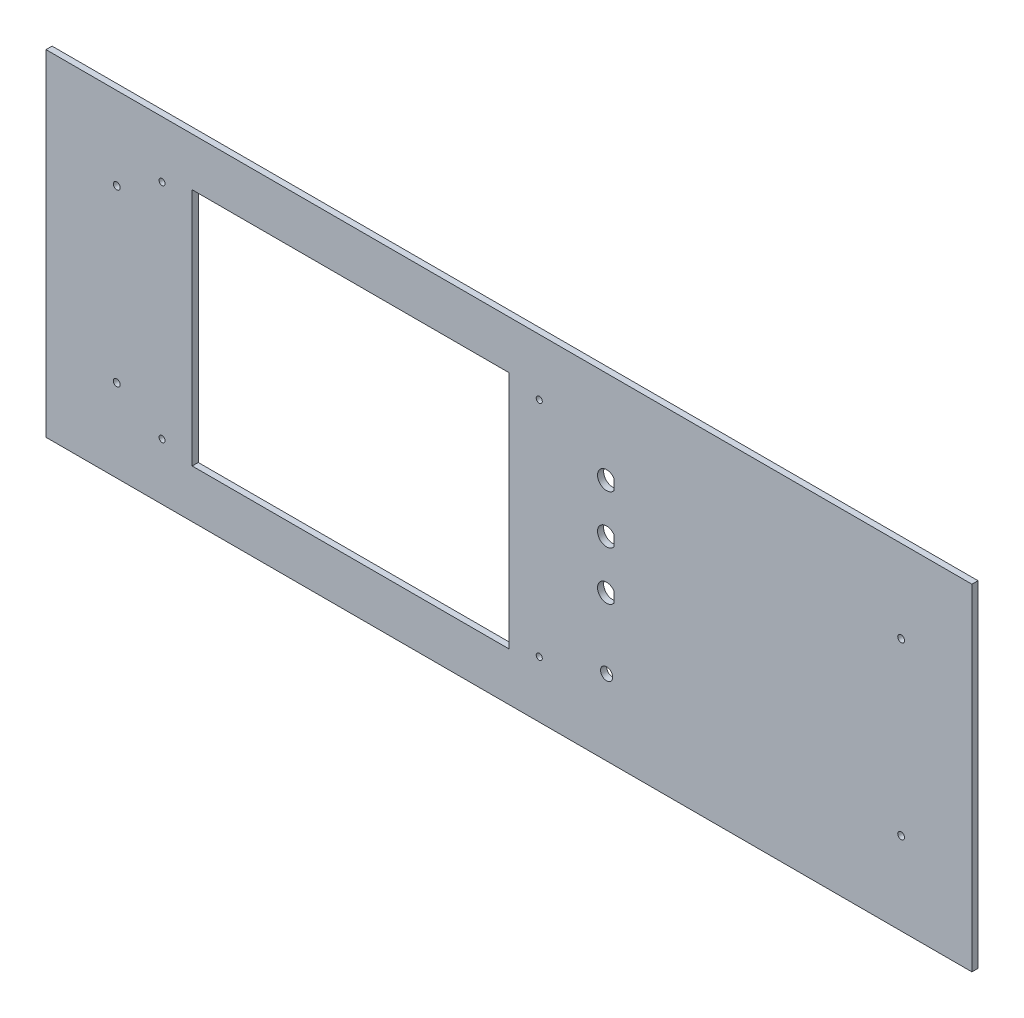
SolidWorks part; units mm, degrees
ref_plane "Front" through (0, 0, 0) normal (0, 0, 1) x (1, 0, 0)
ref_plane "Top" through (0, 0, 0) normal (0, 1, 0) x (1, 0, 0)
ref_plane "Right" through (0, 0, 0) normal (1, 0, 0) x (0, 0, -1)
sketch "Sketch1" plane through (0, 0, 0) normal (0, 0, 1) x (1, 0, 0)
  line L1 (0, 0) -> (482.6, 0)
  line L2 (0, 0) -> (0, 175.006)
  line L3 (0, 175.006) -> (482.6, 175.006)
  line L4 (482.6, 0) -> (482.6, 175.006)
  dimension "D1" = 175.006
  dimension "D2" = 482.6
sheet metal parameters "Sheet-Metal1" thickness 3.175 parameters "D1"=0.7366
base flange "Base-Flange" sketch "Sketch1" thickness 3.175 parameters "D1"=0.7366
ref_plane "Plane1" through (242.0937, 0, 0) normal (1, 0, 0) x (0, 0, -1)
sketch "Sketch2" plane through (0, 0, 3.175) normal (0, 0, 1) x (1, 0, 0)
  line L0 (482.6, 175.006) -> (0, 175.006) construction
  line L1 (76.2, 149.8473) -> (241.4016, 149.8473)
  line L2 (76.2, 149.8473) -> (76.2, 25.1587)
  line L3 (76.2, 25.1587) -> (241.4016, 25.1587)
  line L4 (241.4016, 149.8473) -> (241.4016, 25.1587)
  line L5 (0, 175.006) -> (0, 0) construction
  dimension "D1" = 165.2016
  dimension "D2" = 124.6886
  dimension "D3" = 25.1587
  dimension "D4" = 76.2
extrude "Cut-Extrude1" cut sketch "Sketch2" against normal through all normal cut yes
hole_wizard "1/8 (0.125) Diameter Hole1" positions "3DSketch1" profile "Sketch3" hole size "1/8" standard "Ansi Inch" end condition through all
sketch3d "3DSketch1"
  line L0 (76.2, 25.1587, 3.175) -> (241.4016, 25.1587, 3.175) construction
  line L1 (76.2, 149.8473, 3.175) -> (76.2, 25.1587, 3.175) construction
  point P0 (60.5028, 29.5021, 3.175)
  dimension "D1" = 4.3434
  dimension "D2" = 15.6972
sketch "Sketch3" plane through (60.5028, 29.5021, 3.175) normal (1, 0, 0) x (0, -1, 0)
  line L0 (0, 0) -> (0, 3.175)
  line L1 (0, 3.175) -> (1.5875, 3.175)
  line L2 (1.5875, 3.175) -> (1.5875, 0)
  line L5 (1.5875, 0) -> (0, 0)
  line L11 (0, -6.35) -> (0, 107.95) construction
  dimension "Thru Hole Dia." = 3.175
  dimension "Thru Hole Depth" = 3.175
pattern_linear "LPattern1" count 2 spacing 116.0018 along (0, 1, 0) count 2 spacing 196.596 along (1, 0, 0) of "1/8 (0.125) Diameter Hole1"
sketch "Sketch4" plane through (0, 0, 3.175) normal (0, 0, 1) x (1, 0, 0)
  line L0 (241.4016, 25.1587) -> (241.4016, 149.8473) construction
  line L1 (76.2, 25.1587) -> (241.4016, 25.1587) construction
  line L2 (296.1513, 73.3434) -> (296.1513, 78.574)
  arc A0 (296.1513, 78.574) -> (296.1513, 73.3434) centre (292.2016, 75.9587) ccw
  dimension "D1" = 50.8
  dimension "D2" = 50.8
  dimension "D3" = 8.6868
extrude "Cut-Extrude2" cut sketch "Sketch4" against normal through all normal cut yes
pattern_linear "LPattern2" count 3 spacing 25.4 along (0, 1, 0) of "Cut-Extrude2"
sketch "Sketch5" plane through (0, 0, 3.175) normal (0, 0, 1) x (1, 0, 0)
  line L0 (241.4016, 25.1587) -> (241.4016, 149.8473) construction
  line L1 (76.2, 25.1587) -> (241.4016, 25.1587) construction
  circle A0 centre (292.2016, 39.3827) radius 3.175
  dimension "D1" = 50.8
  dimension "D2" = 14.224
extrude "Cut-Extrude3" cut sketch "Sketch5" against normal through all normal cut yes
hole_wizard "#40 (0.098) Diameter Hole1" positions "3DSketch2" profile "Sketch6" hole size "#40" standard "Ansi Inch"
sketch3d "3DSketch2"
  line L0 (0, 175.006, 3.175) -> (0, 0, 3.175) construction
  line L1 (0, 0, 3.175) -> (482.6, 0, 3.175) construction
  point P0 (36.8808, 43.053, 3.175)
  dimension "D1" = 36.8808
  dimension "D2" = 43.053
sketch "Sketch6" plane through (36.8808, 43.053, 3.175) normal (1, 0, 0) x (0, -1, 0)
  line L0 (0, 0) -> (0, 4.1925)
  line L1 (0, 4.1925) -> (1.778, 3.1242)
  line L2 (1.778, 3.1242) -> (1.778, 0)
  line L5 (1.778, 0) -> (0, 0)
  line L10 (0, 4.1925) -> (-1.778, 3.1242) construction
  line L11 (0, -6.35) -> (0, 107.95) construction
  dimension "Hole Dia." = 3.556
  dimension "Hole Depth" = 3.1242
  dimension "Drill Angle" = 118
pattern_linear "LPattern3" count 2 spacing 408.8384 along (1, 0, 0) count 2 spacing 88.9 along (0, 1, 0) of "#40 (0.098) Diameter Hole1"
flat pattern "Flat-Pattern1" [suppressed]
sketch "Bend-Lines1" plane through (0, 0, 0) normal (0, 1, 0) x (-1, 0, 0)
